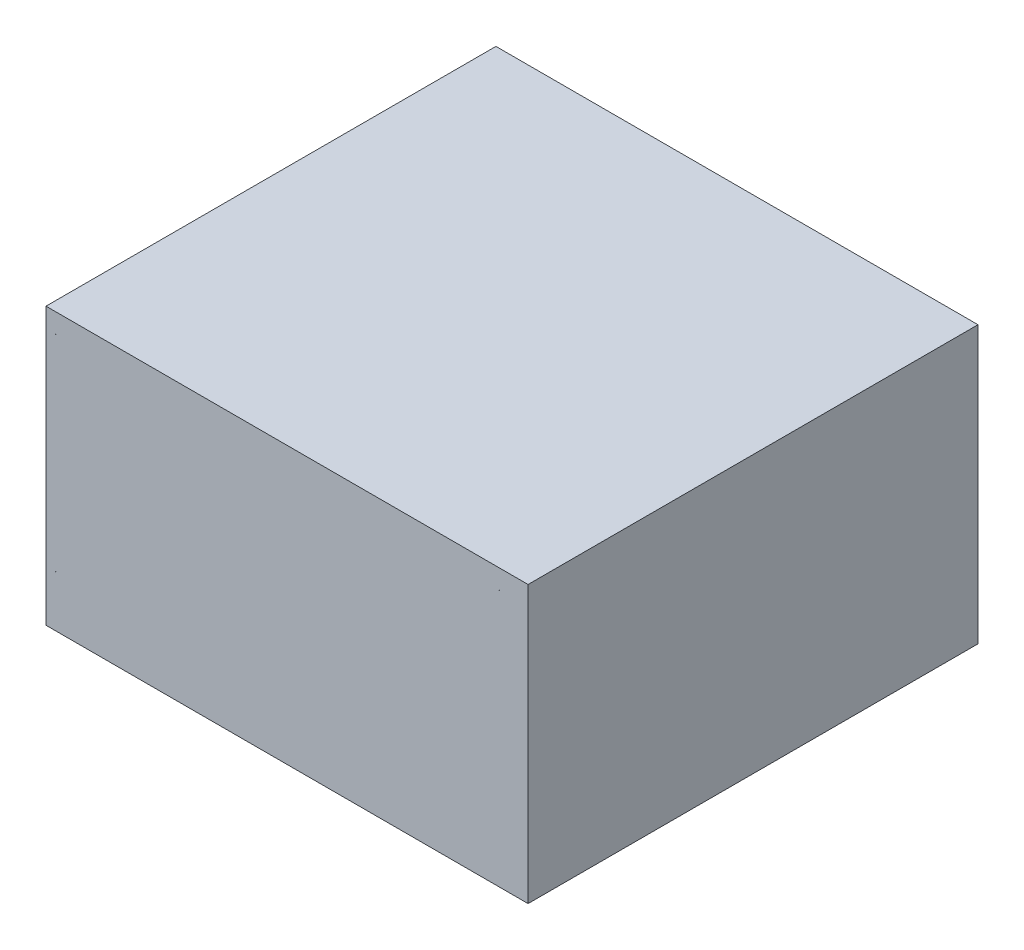
SolidWorks part; units mm, degrees
ref_plane "정면" through (0, 0, 0) normal (0, 0, 1) x (1, 0, 0)
ref_plane "윗면" through (0, 0, 0) normal (0, 1, 0) x (1, 0, 0)
ref_plane "우측면" through (0, 0, 0) normal (1, 0, 0) x (0, 0, -1)
sketch "스케치1" plane through (0, 0, 0) normal (0, 0, 1) x (1, 0, 0)
  line L1 (0, 0) -> (3810, 0)
  line L2 (0, 0) -> (0, 2184.4)
  line L3 (0, 2184.4) -> (3810, 2184.4)
  line L4 (3810, 0) -> (3810, 2184.4)
  line L5 (76.2, 2032) -> (3581.4, 2032) construction
  line L6 (76.2, 2032) -> (76.2, 406.4) construction
  line L7 (76.2, 406.4) -> (3581.4, 406.4) construction
  line L8 (3581.4, 2032) -> (3581.4, 406.4) construction
  circle A0 centre (76.2, 2032) radius 1.7526
  circle A1 centre (3581.4, 2032) radius 1.7526
  circle A2 centre (76.2, 406.4) radius 1.7526
  circle A3 centre (2971.8, 152.4) radius 1.7526
  dimension "D7" = 3.5052
  dimension "D1" = 3810
  dimension "D2" = 2184.4
  dimension "D3" = 1625.6
  dimension "D4" = 406.4
  dimension "D5" = 3505.2
  dimension "D6" = 152.4
  dimension "D8" = 2895.6
  dimension "D9" = 152.4
extrude "보스-돌출1" add sketch "스케치1" against normal blind 3556 contours A3 | L1 L4 L3 L2 A3 A2 A1 A0 | A1 | A2 | A0 region at (1905.0011, 1092.1997, 0) region at (76.2, 2032, 0) region at (3581.4, 2032, 0) region at (76.2, 406.4, 0) region at (2971.8, 152.4, 0)
extrude "컷-돌출1" cut sketch "스케치1<3>" against normal blind 127 contours A0 | A1 | A2 | A3 region at (76.2, 2032, 0) region at (3581.4, 2032, 0) region at (76.2, 406.4, 0) region at (2971.8, 152.4, 0)
sketch "스케치1<3>" plane through (0, 0, 0) normal (0, 0, 1) x (1, 0, 0) same geometry as "스케치1"
